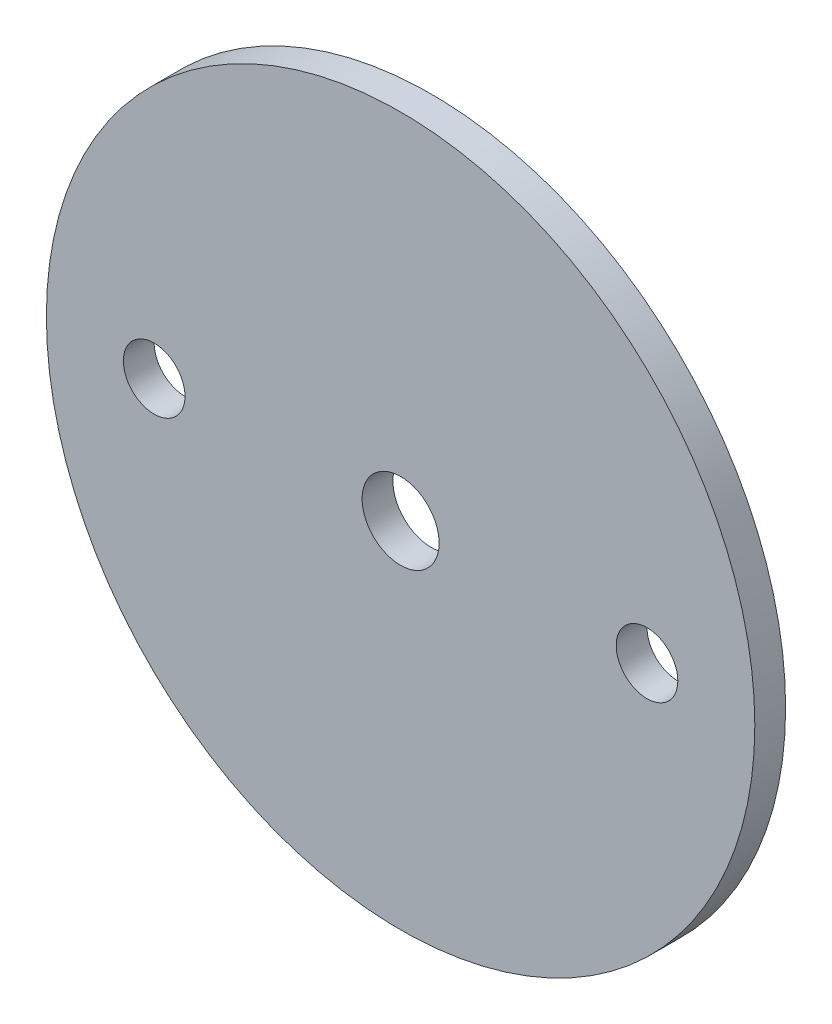
SolidWorks part; units mm, degrees
ref_plane "Front Plane" through (0, 0, 0) normal (0, 0, 1) x (1, 0, 0)
ref_plane "Top Plane" through (0, 0, 0) normal (0, 1, 0) x (1, 0, 0)
ref_plane "Right Plane" through (0, 0, 0) normal (1, 0, 0) x (0, 0, -1)
sketch "Sketch1" plane through (0, 0, 0) normal (0, 0, 1) x (1, 0, 0)
  circle A0 centre (0, 0) radius 36.5125
  dimension "D1" = 73.025
extrude "Boss-Extrude1" add sketch "Sketch1" along normal mid plane 3.175
sketch "Sketch2" plane through (0, 0, 1.5875) normal (0, 0, 1) x (1, 0, 0)
  line L0 (-1000, 0) -> (49000, 0) construction
  line L1 (0, -1000) -> (0, 49000) construction
  point P4 (25.4, 0)
  point P5 (-25.4, 0)
  dimension "D2" = 50.8
  dimension "D1" = 25.4
hole_wizard "1/4 (0.25) Diameter Hole1" positions "Sketch2" profile "Sketch3" hole size "1/4" standard "ANSI Inch" end condition through all
sketch "Sketch3" plane through (-25.4, 0, 1.5875) normal (1, 0, 0) x (0, -1, 0)
  line L0 (0, 0) -> (0, 3.175)
  line L1 (0, 3.175) -> (3.175, 3.175)
  line L2 (3.175, 3.175) -> (3.175, 0)
  line L5 (3.175, 0) -> (0, 0)
  line L11 (0, -6.35) -> (0, 107.95) construction
  dimension "Thru Hole Dia." = 6.35
  dimension "Thru Hole Depth" = 3.175
sketch "Sketch4" plane through (0, 0, 1.5875) normal (0, 0, 1) x (1, 0, 0)
  point P0 (0, 0)
hole_wizard "5/16 (0.3125) Diameter Hole1" positions "Sketch4" profile "Sketch5" hole size "5/16" standard "ANSI Inch"
sketch "Sketch5" plane through (0, 0, 1.5875) normal (1, 0, 0) x (0, -1, 0)
  line L0 (0, 0) -> (0, 3.302)
  line L1 (0, 3.302) -> (3.9687, 3.302)
  line L2 (3.9687, 3.302) -> (3.9688, 0)
  line L5 (3.9688, 0) -> (0, 0)
  line L10 (0, 3.302) -> (-3.9688, 3.302) construction
  line L11 (0, -6.35) -> (0, 107.95) construction
  dimension "Hole Dia." = 7.9375
  dimension "Hole Depth" = 3.302
  dimension "Drill Angle" = 180
equation "\"AIRFRAME_OD\"= 3.091in"
equation "\"AIRFRAME_ID\"= 3.00in"
equation "\"FLAT_T\"= 0.125in"
equation "\"NOSE_EXP_L\"= 3.5in"
equation "\"NOSE_SHOULDER_L\"= 5in"
equation "\"MAIN_L\"= 30in"
equation "\"RECO_COUP_L\"= 6in"
equation "\"RECO_SWITCH_L\"= 1.5in"
equation "\"DROGUE_L\"= 14in"
equation "\"ATS_FORE_COUP_L\"= 4in"
equation "\"ATS_AFT_COUP_L\"= 4in"
equation "\"LOWER_L\"= 16in"
equation "\"FIN_N\"= 4"
equation "\"CR_AFT_X\"= 0.5in"
equation "\"CR_FORE_X\"= 6in"
equation "\"FIN_ROOT\"= 5in"
equation "\"FIN_X\"= 0.75in"
equation "\"MOTOR_OD\"= 2.25in"
equation "\"MOTOR_ID\"= 2.126in"
equation "\"COUPLER_OD\"= 2.998in"
equation "\"COUPLER_ID\"= 2.875in"
equation "\"D1@Sketch1\"=\"COUPLER_ID\""
equation "\"D1@Boss-Extrude1\"=\"FLAT_T\""
equation "\"RECO_ROD_X\"= 1.5in"
equation "\"ATS_ROD_X\"= 2in"
equation "\"D2@Sketch2\"=\"ATS_ROD_X\""
